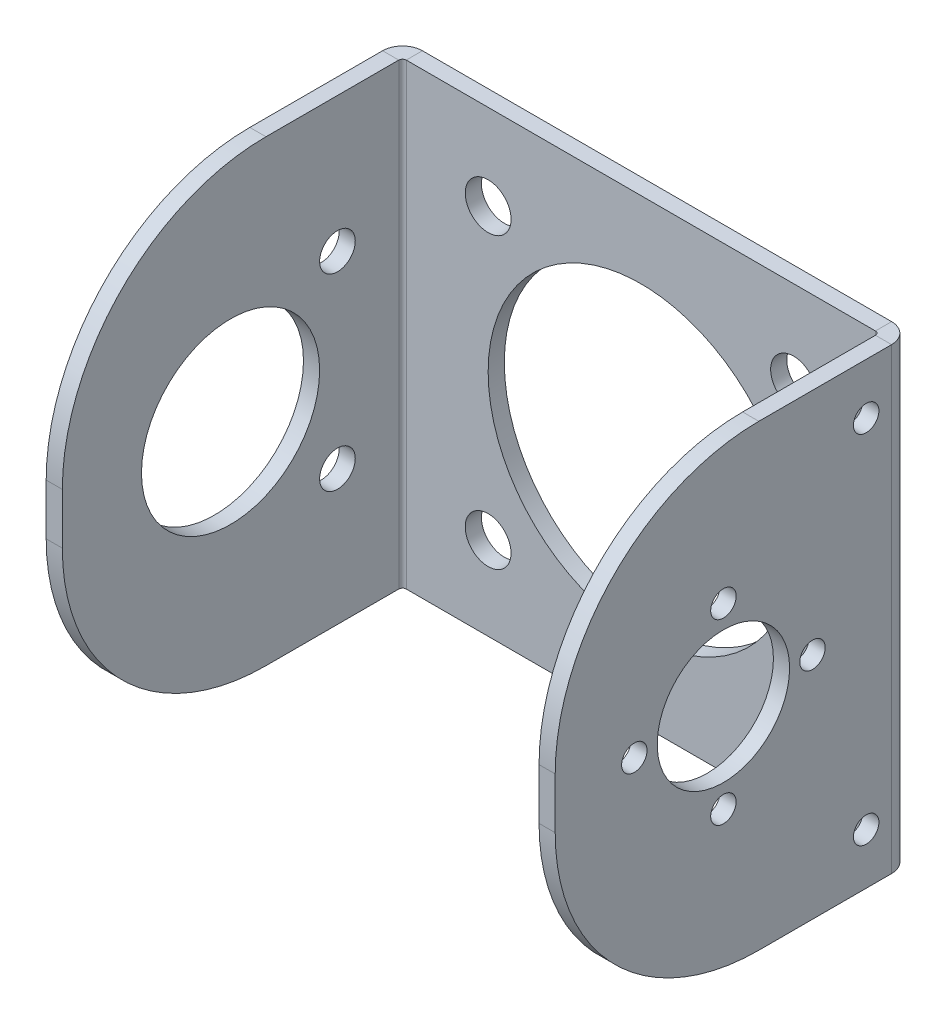
SolidWorks part; units mm, degrees
note: The reader was unsure of these and kept them because the rebuilt part matched: thickness of "Brida base4", "Brida de arista1", "Sheet-Metal7", "Sheet-Metal8", "Sheet-Metal9", "Sheet-Metal10", "Sheet-Metal11", "Sheet-Metal12", "Sheet-Metal15"; flange length of "Brida de arista1".
material "AISI 1020 Acero laminado en frío"
ref_plane "Alzado" through (0, 0, 0) normal (0, 0, 1) x (1, 0, 0)
ref_plane "Planta" through (0, 0, 0) normal (0, 1, 0) x (1, 0, 0)
ref_plane "Vista lateral" through (0, 0, 0) normal (1, 0, 0) x (0, 0, -1)
sketch "Croquis22" plane through (0, 0, 0) normal (0, 0, 1) x (1, 0, 0)
  line L1 (-50, 45) -> (50, 45)
  line L2 (-50, 45) -> (-50, -45)
  line L3 (-50, -45) -> (50, -45)
  line L4 (50, 45) -> (50, -45)
  line L5 (-50, 45) -> (50, -45) construction
  line L6 (-50, -45) -> (50, 45) construction
  point P0 (0, 0)
  dimension "D1" = 100
  dimension "D2" = 90
base flange "Brida base4" sketch "Croquis22" thickness 3.175 reverse thickness direction no parameters "D1"=0.7366
edge flange "Brida de arista1" sketch "Croquis31" flange profiles "Croquis31", "Croquis32" flange angle 90 flange length 70 flange position material inside bend radius 0.7366 thickness 3.175 relief rectangular parameters "D6"=10, "D8"=1
sketch "Croquis31" plane through (-50, 0, 0) normal (-1, 0, 0) x (0, -1, 0)
  line L2 (-45, 0) -> (-45, 66.825)
  line L3 (-45, 66.825) -> (45, 66.825)
  line L4 (45, 66.825) -> (45, 0)
  line L35 (-45, 0) -> (45, 0) construction
  line L36 (-45, 0) -> (45, 0)
sketch "Croquis32" plane through (50, 0, 0) normal (1, 0, 0) x (0, 1, 0)
  line L2 (-45, 0) -> (-45, 66.825)
  line L3 (-45, 66.825) -> (45, 66.825)
  line L4 (45, 66.825) -> (45, 0)
  line L39 (-45, 0) -> (45, 0) construction
  line L40 (-45, 0) -> (45, 0)
bend "Pliegue de arista1" bend radius 0.7366 bend angle 90 parameters "D5"=1
bend "Pliegue de arista2" bend radius 0.7366 bend angle 90 parameters "D5"=2
sketch "Croquis33" plane through (-50, 0, 0) normal (-1, 0, 0) x (0, 0, 1)
  line L0 (33.7808, 45) -> (33.7808, -45) construction
  line L1 (66.825, 45) -> (0.7366, 45) construction
  line L2 (0.7366, -45) -> (66.825, -45) construction
  line L5 (33.7808, 0) -> (12.7808, 0) construction
  line L8 (12.7808, 18.5) -> (12.7808, -18.5)
  circle A0 centre (33.7808, 0) radius 8
  circle A1 centre (12.7808, 18.5) radius 3.5
  circle A2 centre (12.7808, -18.5) radius 3.5
  point P12 (12.7808, 0)
  dimension "D1" = 16
  dimension "D4" = 7
  dimension "D5" = 7
  dimension "D2" = 21
  dimension "D3" = 18.5
extrude "Cortar-Extruir3" cut sketch "Croquis33" against normal blind 14.7625 contours A0 | A1 | A2 normal cut yes
sketch "Croquis35" plane through (50, 0, 0) normal (1, 0, 0) x (0, 0, -1)
  line L0 (-33.7808, 45) -> (-33.7808, -45) construction
  line L1 (-0.7366, 45) -> (-66.825, 45) construction
  line L2 (-66.825, -45) -> (-0.7366, -45) construction
  circle A0 centre (-33.7808, 0) radius 13
  circle A1 centre (-33.7808, 0) radius 17.5 construction
  circle A2 centre (-33.7808, 17.5) radius 2.5
  circle A3 centre (-33.7808, -17.5) radius 2.5
  circle A4 centre (-16.2808, 0) radius 2.5
  circle A5 centre (-51.2808, 0) radius 2.5
  dimension "D1" = 26
  dimension "D2" = 35
  dimension "D3" = 5
  dimension "D4" = 5
  dimension "D5" = 5
  dimension "D6" = 5
extrude "Cortar-Extruir4" cut sketch "Croquis35" against normal blind 14.7625 normal cut yes
sketch "Croquis36" plane through (-50, 0, 0) normal (-1, 0, 0) x (0, 0, 1)
  circle A0 centre (33.7808, 0) radius 17.5
  dimension "D1" = 35
extrude "Cortar-Extruir5" cut sketch "Croquis36" against normal blind 14.7625 normal cut yes
sketch "Croquis37" plane through (0, 0, 0) normal (0, 0, 1) x (1, 0, 0)
  line L0 (-30, 45) -> (-30, -45) construction
  line L1 (46.0884, 45) -> (-46.0884, 45) construction
  line L2 (-46.0884, -45) -> (46.0884, -45) construction
  line L3 (30, 45) -> (30, -45) construction
  line L4 (0, 45) -> (0, -45) construction
  line L5 (-50, 45) -> (-50, -45) construction
  line L6 (50, 45) -> (50, -45) construction
  line L7 (-46.0884, 0) -> (46.825, 0) construction
  line L8 (-46.0884, -45) -> (-46.0884, 45) construction
  line L9 (46.825, -45) -> (46.825, 45) construction
  line L10 (0, 45) -> (0, -45) construction
  circle A0 centre (-30, 28.1815) radius 4.5
  circle A1 centre (-30, -28.6219) radius 4.5
  circle A2 centre (30, 28.1815) radius 4.5
  circle A3 centre (30, -28.6219) radius 4.5
  circle A10 centre (0, 0) radius 30
  dimension "D3" = 9
  dimension "D4" = 9
  dimension "D5" = 9
  dimension "D6" = 9
  dimension "D7" = 60
  dimension "D1" = 20
  dimension "D2" = 20
  dimension "D9" = 30
extrude "Cortar-Extruir6" cut sketch "Croquis37" against normal blind 14.7625 normal cut yes
fillet "Redondeo1" radius 40 4 edges at (48.4125, -45, 66.825) (48.4125, 45, 66.825) (-48.4125, 45, 66.825) (-48.4125, -45, 66.825)
sketch "Croquis40" plane through (50, 0, 0) normal (1, 0, 0) x (0, 0, -1)
  line L0 (-0.7366, 45) -> (-0.7366, -45) construction
  line L1 (-0.7366, 45) -> (-26.825, 45) construction
  line L2 (-26.825, -45) -> (-0.7366, -45) construction
  circle A0 centre (-5.7366, 35) radius 2.5
  circle A1 centre (-5.7366, -35) radius 2.5
  dimension "D1" = 5
  dimension "D2" = 5
  dimension "D3" = 5
  dimension "D4" = 5
  dimension "D5" = 10
  dimension "D6" = 10
extrude "Cortar-Extruir7" cut sketch "Croquis40" against normal blind 14.7625 normal cut yes
sketch "Bend-Lines5" [suppressed] plane through (0, 0, 0) normal (0, 1, 0) x (1, 0, 0)
sketch "Bounding-Box5" [suppressed] plane through (0, 0, 0) normal (0, 1, 0) x (1, 0, 0)
sheet metal parameters "Sheet-Metal7" thickness 3.175 parameters "D1"=0.7366
flat pattern "Flat-Pattern7" [suppressed]
sketch "Bend-Lines6" plane through (0, 0, 0) normal (0, 1, 0) x (1, 0, 0)
sketch3d "Bounding-Box6" [suppressed]
  line L0 (150, -45, 0) -> (-150, -45, 0) construction
  line L1 (150, 45, 0) -> (-150, 45, 0) construction
  line L2 (150, -45, 0) -> (150, 45, 0) construction
  line L3 (-150, -45, 0) -> (-150, 45, 0) construction
sheet metal parameters "Sheet-Metal8" thickness 3.175 parameters "D1"=0.7366, "D7"=4.76
flat pattern "Flat-Pattern7" [suppressed]
sketch "Bend-Lines6" plane through (0, 0, 0) normal (0, 0, 1) x (1, 0, 0)
  line L0 (96.9512, -45) -> (96.9512, 45) construction
  line L1 (-96.9512, 45) -> (-96.9512, -45) construction
  line L2 (96.9512, -45) -> (96.9512, 45) construction
  line L3 (-96.9512, 45) -> (-96.9512, -45) construction
sketch3d "Bounding-Box6" [suppressed]
  line L0 (-163.9023, -45, 0) -> (163.9023, -45, 0) construction
  line L1 (-163.9023, 45, 0) -> (163.9023, 45, 0) construction
  line L2 (-163.9023, -45, 0) -> (-163.9023, 45, 0) construction
  line L3 (163.9023, -45, 0) -> (163.9023, 45, 0) construction
bend of the flat pattern "Aplanar-<Pliegue de arista1>1"
bend of the flat pattern "Aplanar-<Pliegue de arista2>1"
sketch "Croquis33-1" [suppressed] plane through (-98.6623, 0, -4.76) normal (0, 0, -1) x (-1, 0, 0)
  line L0 (32.9883, 45) -> (32.9883, -45) construction
  line L5 (32.9883, 0) -> (11.9883, 0) construction
  circle A0 centre (32.9883, 0) radius 8
  dimension "D1" = 16
  dimension "D2" = 21
sheet metal parameters "Sheet-Metal9" thickness 3.175 parameters "D1"=0.7366, "D7"=4.76
flat pattern "Flat-Pattern7" [suppressed]
sketch "Bend-Lines6" plane through (0, 0, 0) normal (0, 0, 1) x (1, 0, 0)
  line L0 (96.9512, -45) -> (96.9512, 45) construction
  line L1 (-96.9512, 45) -> (-96.9512, -45) construction
  line L2 (96.9512, -45) -> (96.9512, 45) construction
  line L3 (-96.9512, 45) -> (-96.9512, -45) construction
sketch3d "Bounding-Box6" [suppressed]
  line L0 (-163.9023, -45, 0) -> (163.9023, -45, 0) construction
  line L1 (-163.9023, 45, 0) -> (163.9023, 45, 0) construction
  line L2 (-163.9023, -45, 0) -> (-163.9023, 45, 0) construction
  line L3 (163.9023, -45, 0) -> (163.9023, 45, 0) construction
bend of the flat pattern "Aplanar-<Pliegue de arista1>1"
bend of the flat pattern "Aplanar-<Pliegue de arista2>1"
sketch "Croquis33-1" [suppressed] plane through (-98.6623, 0, -4.76) normal (0, 0, -1) x (-1, 0, 0)
  line L0 (32.9883, 45) -> (32.9883, -45) construction
  line L5 (32.9883, 0) -> (11.9883, 0) construction
  line L8 (11.9883, 18.5) -> (11.9883, -18.5)
  circle A0 centre (32.9883, 0) radius 8
  circle A1 centre (11.9883, 18.5) radius 3.5
  circle A2 centre (11.9883, -18.5) radius 3.5
  point P12 (11.9883, 0)
  dimension "D1" = 16
  dimension "D4" = 7
  dimension "D5" = 7
  dimension "D2" = 21
  dimension "D3" = 18.5
sheet metal parameters "Sheet-Metal10" thickness 3.175 parameters "D1"=0.7366, "D7"=4.76
flat pattern "Flat-Pattern7" [suppressed]
sketch "Bend-Lines6" plane through (0, 0, 0) normal (0, 0, 1) x (1, 0, 0)
  line L0 (96.9512, -45) -> (96.9512, 45) construction
  line L1 (-96.9512, 45) -> (-96.9512, -45) construction
  line L2 (96.9512, -45) -> (96.9512, 45) construction
  line L3 (-96.9512, 45) -> (-96.9512, -45) construction
sketch3d "Bounding-Box6" [suppressed]
  line L0 (-163.9023, -45, 0) -> (163.9023, -45, 0) construction
  line L1 (-163.9023, 45, 0) -> (163.9023, 45, 0) construction
  line L2 (-163.9023, -45, 0) -> (-163.9023, 45, 0) construction
  line L3 (163.9023, -45, 0) -> (163.9023, 45, 0) construction
bend of the flat pattern "Aplanar-<Pliegue de arista1>1"
bend of the flat pattern "Aplanar-<Pliegue de arista2>1"
sketch "Croquis33-1" [suppressed] plane through (-98.6623, 0, -4.76) normal (0, 0, -1) x (-1, 0, 0)
  line L0 (32.9883, 45) -> (32.9883, -45) construction
  line L5 (32.9883, 0) -> (11.9883, 0) construction
  line L8 (11.9883, 18.5) -> (11.9883, -18.5)
  circle A0 centre (32.9883, 0) radius 8
  circle A1 centre (11.9883, 18.5) radius 3.5
  circle A2 centre (11.9883, -18.5) radius 3.5
  point P12 (11.9883, 0)
  dimension "D1" = 16
  dimension "D4" = 7
  dimension "D5" = 7
  dimension "D2" = 21
  dimension "D3" = 18.5
sheet metal parameters "Sheet-Metal11" thickness 3.175 parameters "D1"=0.7366, "D7"=4.76
flat pattern "Flat-Pattern7" [suppressed]
sketch "Bend-Lines6" plane through (0, 0, 0) normal (0, 0, 1) x (1, 0, 0)
  line L0 (96.9512, -45) -> (96.9512, 45) construction
  line L1 (-96.9512, 45) -> (-96.9512, -45) construction
  line L2 (96.9512, -45) -> (96.9512, 45) construction
  line L3 (-96.9512, 45) -> (-96.9512, -45) construction
sketch3d "Bounding-Box6" [suppressed]
  line L0 (-163.9023, -45, 0) -> (163.9023, -45, 0) construction
  line L1 (-163.9023, 45, 0) -> (163.9023, 45, 0) construction
  line L2 (-163.9023, -45, 0) -> (-163.9023, 45, 0) construction
  line L3 (163.9023, -45, 0) -> (163.9023, 45, 0) construction
bend of the flat pattern "Aplanar-<Pliegue de arista1>1"
bend of the flat pattern "Aplanar-<Pliegue de arista2>1"
sketch "Croquis33-1" [suppressed] plane through (-98.6623, 0, -4.76) normal (0, 0, -1) x (-1, 0, 0)
  line L0 (32.9883, 45) -> (32.9883, -45) construction
  line L5 (32.9883, 0) -> (11.9883, 0) construction
  line L8 (11.9883, 18.5) -> (11.9883, -18.5)
  circle A0 centre (32.9883, 0) radius 8
  circle A1 centre (11.9883, 18.5) radius 3.5
  circle A2 centre (11.9883, -18.5) radius 3.5
  point P12 (11.9883, 0)
  dimension "D1" = 16
  dimension "D4" = 7
  dimension "D5" = 7
  dimension "D2" = 21
  dimension "D3" = 18.5
sheet metal parameters "Sheet-Metal12" thickness 3.175 parameters "D1"=0.7366, "D7"=4.76
flat pattern "Flat-Pattern7" [suppressed]
sketch "Bend-Lines6" plane through (0, 0, 0) normal (0, 0, 1) x (1, 0, 0)
  line L0 (47.9137, -45) -> (47.9137, 45) construction
  line L1 (-47.9137, 45) -> (-47.9137, -45) construction
  line L2 (47.9137, -45) -> (47.9137, 45) construction
  line L3 (-47.9137, 45) -> (-47.9137, -45) construction
sketch3d "Bounding-Box6" [suppressed]
  line L0 (-115.8275, -45, 0) -> (115.8275, -45, 0) construction
  line L1 (-115.8275, 45, 0) -> (115.8275, 45, 0) construction
  line L2 (-115.8275, -45, 0) -> (-115.8275, 45, 0) construction
  line L3 (115.8275, -45, 0) -> (115.8275, 45, 0) construction
bend of the flat pattern "Aplanar-<Pliegue de arista1>1"
bend of the flat pattern "Aplanar-<Pliegue de arista2>1"
sketch "Croquis33-1" [suppressed] plane through (-49.0025, 0, -3.175) normal (0, 0, -1) x (-1, 0, 0)
  line L0 (33.7808, 45) -> (33.7808, -45) construction
  line L5 (33.7808, 0) -> (12.7808, 0) construction
  line L8 (12.7808, 18.5) -> (12.7808, -18.5)
  circle A0 centre (33.7808, 0) radius 8
  circle A1 centre (12.7808, 18.5) radius 3.5
  circle A2 centre (12.7808, -18.5) radius 3.5
  point P12 (12.7808, 0)
  dimension "D1" = 16
  dimension "D4" = 7
  dimension "D5" = 7
  dimension "D2" = 21
  dimension "D3" = 18.5
sheet metal parameters "Sheet-Metal15" thickness 3.175 parameters "D1"=0.7366, "D7"=4.76
flat pattern "Flat-Pattern7" [suppressed]
sketch "Bend-Lines6" plane through (0, 0, 0) normal (0, 0, 1) x (1, 0, 0)
  line L0 (47.9137, -45) -> (47.9137, 45) construction
  line L1 (-47.9137, 45) -> (-47.9137, -45) construction
  line L2 (47.9137, -45) -> (47.9137, 45) construction
  line L3 (-47.9137, 45) -> (-47.9137, -45) construction
sketch3d "Bounding-Box6" [suppressed]
  line L0 (-115.8275, -45, 0) -> (115.8275, -45, 0) construction
  line L1 (-115.8275, 45, 0) -> (115.8275, 45, 0) construction
  line L2 (-115.8275, -45, 0) -> (-115.8275, 45, 0) construction
  line L3 (115.8275, -45, 0) -> (115.8275, 45, 0) construction
bend of the flat pattern "Aplanar-<Pliegue de arista1>1"
bend of the flat pattern "Aplanar-<Pliegue de arista2>1"
sketch "Croquis33-1" plane through (-49.0025, 0, -3.175) normal (0, 0, -1) x (-1, 0, 0)
  line L0 (33.7808, 45) -> (33.7808, -45) construction
  line L5 (33.7808, 0) -> (12.7808, 0) construction
  line L8 (12.7808, 18.5) -> (12.7808, -18.5)
  circle A0 centre (33.7808, 0) radius 8
  circle A1 centre (12.7808, 18.5) radius 3.5
  circle A2 centre (12.7808, -18.5) radius 3.5
  point P12 (12.7808, 0)
  dimension "D1" = 16
  dimension "D4" = 7
  dimension "D5" = 7
  dimension "D2" = 21
  dimension "D3" = 18.5
